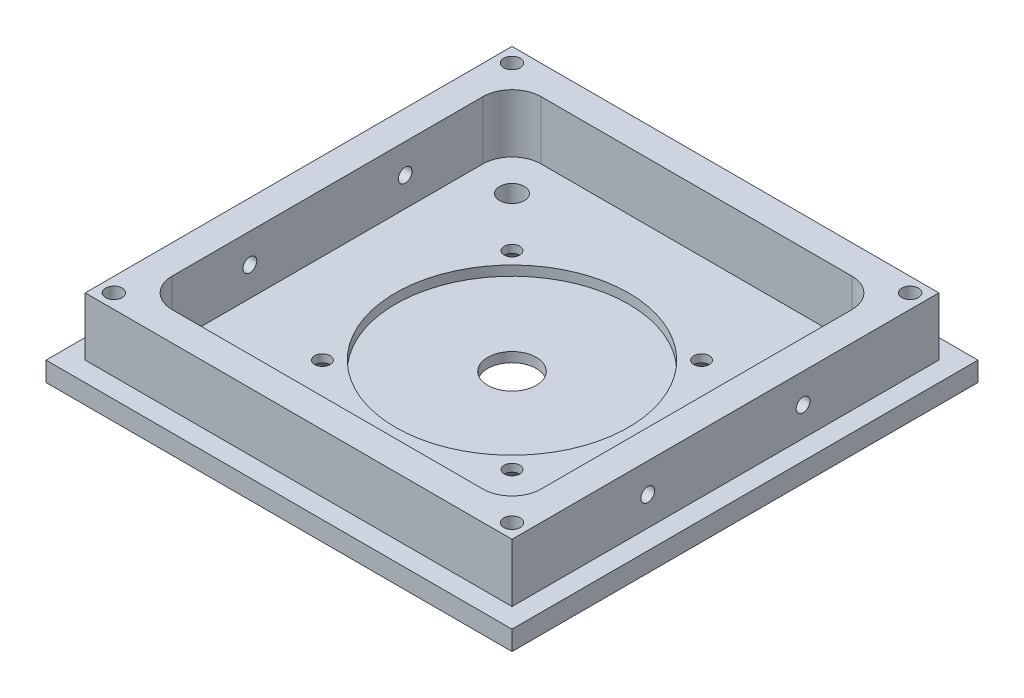
SolidWorks part; units mm, degrees
material "6061-T6 (SS)"
ref_plane "Front Plane" through (0, 0, 0) normal (0, 0, 1) x (1, 0, 0)
ref_plane "Top Plane" through (0, 0, 0) normal (0, 1, 0) x (1, 0, 0)
ref_plane "Right Plane" through (0, 0, 0) normal (1, 0, 0) x (0, 0, -1)
sketch "Sketch1" plane through (0, 0, 0) normal (0, 1, 0) x (1, 0, 0)
  line L1 (-38.1, -38.1) -> (38.1, -38.1)
  line L2 (-38.1, -38.1) -> (-38.1, 38.1)
  line L3 (-38.1, 38.1) -> (38.1, 38.1)
  line L4 (38.1, -38.1) -> (38.1, 38.1)
  line L5 (-38.1, -38.1) -> (38.1, 38.1) construction
  line L6 (-38.1, 38.1) -> (38.1, -38.1) construction
  point P0 (0, 0)
  dimension "D1" = 76.2
  dimension "D2" = 76.2
extrude "Boss-Extrude1" add sketch "Sketch1" along normal blind 3.175
sketch "Sketch2" plane through (0, 3.175, 0) normal (0, 1, 0) x (1, 0, 0)
  line L0 (-38.1, 38.1) -> (-38.1, -38.1) construction
  line L1 (34.8971, -34.8971) -> (-34.8971, -34.8971)
  line L2 (34.8971, -34.8971) -> (34.8971, 34.8971)
  line L3 (34.8971, 34.8971) -> (-34.8971, 34.8971)
  line L4 (-34.8971, -34.8971) -> (-34.8971, 34.8971)
  line L5 (34.8971, -34.8971) -> (-34.8971, 34.8971) construction
  line L6 (34.8971, 34.8971) -> (-34.8971, -34.8971) construction
  line L7 (30.1625, -30.1625) -> (-30.1625, -30.1625)
  line L8 (30.1625, -30.1625) -> (30.1625, 30.1625)
  line L9 (30.1625, 30.1625) -> (-30.1625, 30.1625)
  line L10 (-30.1625, -30.1625) -> (-30.1625, 30.1625)
  line L11 (30.1625, -30.1625) -> (-30.1625, 30.1625) construction
  line L12 (30.1625, 30.1625) -> (-30.1625, -30.1625) construction
  line L14 (38.1, 38.1) -> (-38.1, 38.1) construction
  point P0 (0, 0)
  point P6 (0, 0)
  dimension "D1" = 3.2029
  dimension "D2" = 3.2029
  dimension "D3" = 60.325
extrude "Boss-Extrude2" add sketch "Sketch2" along normal blind 9.525
fillet "Fillet1" radius 4.7625 4 edges at (-30.1625, 7.9375, 30.1625) (30.1625, 7.9375, 30.1625) (30.1625, 7.9375, -30.1625) (-30.1625, 7.9375, -30.1625)
sketch "Sketch3" plane through (0, 3.175, 0) normal (0, 1, 0) x (1, 0, 0)
  circle A0 centre (0, 0) radius 19.05
  dimension "D1" = 38.1
extrude "Cut-Extrude1" cut sketch "Sketch3" against normal blind 1.5875
sketch "Sketch4" plane through (0, 1.5875, 0) normal (0, 1, 0) x (1, 0, 0)
  circle A0 centre (0, 0) radius 3.9688
  dimension "D1" = 7.9375
extrude "Cut-Extrude2" cut sketch "Sketch4" against normal through all
sketch "Sketch5" plane through (0, 3.175, 0) normal (0, 1, 0) x (1, 0, 0)
  line L1 (15.5, -15.5) -> (-15.5, -15.5)
  line L2 (15.5, -15.5) -> (15.5, 15.5)
  line L3 (15.5, 15.5) -> (-15.5, 15.5)
  line L4 (-15.5, -15.5) -> (-15.5, 15.5)
  line L5 (15.5, -15.5) -> (-15.5, 15.5) construction
  line L6 (15.5, 15.5) -> (-15.5, -15.5) construction
  line L7 (23.5966, -23.5966) -> (-23.5966, -23.5966)
  line L8 (23.5966, -23.5966) -> (23.5966, 23.5966)
  line L9 (23.5966, 23.5966) -> (-23.5966, 23.5966)
  line L10 (-23.5966, -23.5966) -> (-23.5966, 23.5966)
  line L11 (23.5966, -23.5966) -> (-23.5966, 23.5966) construction
  line L12 (23.5966, 23.5966) -> (-23.5966, -23.5966) construction
  circle A0 centre (-15.5, 15.5) radius 1.2637
  circle A1 centre (15.5, 15.5) radius 1.2637
  circle A2 centre (15.5, -15.5) radius 1.2637
  circle A3 centre (-15.5, -15.5) radius 1.2637
  point P2 (0, 0)
  point P10 (0, 0)
  dimension "D2" = 2.5273
  dimension "D1" = 31
  dimension "D3" = 47.1932
hole_wizard "#39 (0.0995) Diameter Hole1" positions "Sketch7" profile "Sketch6" hole size "#39" standard "ANSI Inch" end condition through all
sketch "Sketch7" plane through (0, 3.175, 0) normal (0, 1, 0) x (1, 0, 0)
  point P0 (15.5, 15.5)
  point P3 (-15.5, 15.5)
  point P6 (-15.5, -15.5)
  point P9 (15.5, -15.5)
  point P12 (-23.5966, 23.5966)
  point P15 (23.5966, 23.5966)
  point P18 (23.5966, -23.5966)
  point P21 (-23.5966, -23.5966)
sketch "Sketch6" plane through (15.5, 3.175, -15.5) normal (1, 0, 0) x (0, 0, 1)
  line L0 (0, 0) -> (0, 3.175)
  line L1 (0, 3.175) -> (1.2636, 3.175)
  line L2 (1.2636, 3.175) -> (1.2636, 0)
  line L5 (1.2636, 0) -> (0, 0)
  line L11 (0, -6.35) -> (0, 107.95) construction
  dimension "Thru Hole Dia." = 2.5273
  dimension "Thru Hole Depth" = 3.175
hole_wizard "#10-32 Tapped Hole1" positions "Sketch17" profile "Sketch15" tap size "#10-32" standard "ANSI Inch" end condition through all
sketch "Sketch17" plane through (0, 3.175, 0) normal (0, 1, 0) x (1, 0, 0)
  point P0 (-23.5966, 23.5966)
  point P3 (23.5966, 23.5966)
  point P6 (23.5966, -23.5966)
  point P9 (-23.5966, -23.5966)
sketch "Sketch15" plane through (-23.5966, 3.175, -23.5966) normal (1, 0, 0) x (0, 0, 1)
  line L0 (0, 0) -> (0, 3.175)
  line L1 (0, 3.175) -> (2.0193, 3.175)
  line L2 (2.0193, 3.175) -> (2.0193, 0)
  line L5 (2.0193, 0) -> (0, 0)
  line L11 (0, -6.35) -> (0, 107.95) construction
  dimension "Thru Tap Drill Dia." = 4.0386
  dimension "Thru Tap Drill Depth" = 3.175
cosmetic thread "Hole Thread3" parameters "D2"=4.826
cosmetic thread "Hole Thread4" parameters "D2"=4.826
cosmetic thread "Hole Thread5" parameters "D2"=4.826
cosmetic thread "Hole Thread6" parameters "D2"=4.826
sketch "Sketch8" plane through (34.8971, 0, 0) normal (1, 0, 0) x (0, 0, -1)
  line L0 (-38.1, 3.175) -> (38.1, 3.175) construction
  point P0 (-12.7, 7.9375)
  dimension "D1" = 4.7625
  dimension "D2" = 12.7
hole_wizard "#4-40 Tapped Hole1" positions "Sketch10" profile "Sketch9" tap size "#4-40" standard "ANSI Inch"
sketch "Sketch10" plane through (34.8971, 0, 0) normal (1, 0, 0) x (0, 0, -1)
  point P0 (-12.7, 7.9375)
sketch "Sketch9" plane through (34.8971, 7.9375, 12.7) normal (0, 1, 0) x (0, 0, -1)
  line L0 (0, 0) -> (0, 7.2832)
  line L1 (0, 7.2832) -> (1.1303, 6.604)
  line L2 (1.1303, 6.604) -> (1.1303, 0)
  line L5 (1.1303, 0) -> (0, 0)
  line L10 (0, 7.2832) -> (-1.1303, 6.604) construction
  line L11 (0, -6.35) -> (0, 107.95) construction
  dimension "Tap Drill Dia." = 2.2606
  dimension "Tap Drill Depth" = 6.604
  dimension "Drill Angle" = 118
cosmetic thread "Hole Thread1" parameters "D1"=2.4486, "D2"=2.8448
mirror "Mirror1" about plane through (0, 0, 0) normal (0, 0, 1) of "#4-40 Tapped Hole1"
mirror "Mirror2" about plane through (0, 0, 0) normal (1, 0, 0) of "Mirror1"
chamfer "Chamfer1" distance 1.905 angle 41 4 edges at (-15.5, 0, -14.2363) (15.5, 0, -14.2364) (15.5, 0, 16.7636) (-15.5, 0, 16.7637) first distance on face at (-15.5, 0, -14.2363) first distance on face at (15.5, 0, -14.2364) first distance on face at (15.5, 0, 16.7636) first distance on face at (-15.5, 0, 16.7637)
sketch "Sketch11" plane through (0, 0, 0) normal (0, -1, 0) x (1, 0, 0)
  circle A0 centre (32.5501, -32.5501) radius 2.032
  dimension "D1" = 4.064
hole_wizard "#6-32 Tapped Hole1" positions "Sketch13" profile "Sketch12" tap size "#6-32" standard "ANSI Inch" end condition through all
sketch "Sketch13" plane through (0, 0, 0) normal (0, -1, 0) x (-1, 0, 0)
  point P0 (-32.5501, 32.5501)
sketch "Sketch12" plane through (32.5501, 0, -32.5501) normal (1, 0, 0) x (0, 0, -1)
  line L0 (0, 0) -> (0, 12.7)
  line L1 (0, 12.7) -> (1.3525, 12.7)
  line L2 (1.3525, 12.7) -> (1.3525, 0)
  line L5 (1.3525, 0) -> (0, 0)
  line L11 (0, -6.35) -> (0, 107.95) construction
  dimension "Thru Tap Drill Dia." = 2.7051
  dimension "Thru Tap Drill Depth" = 12.7
cosmetic thread "Hole Thread2" parameters "D2"=3.5052
pattern_circular "CirPattern1" count 4 over 360 about axis through (0, 0, 0) along (0, 1, 0) of "#6-32 Tapped Hole1"
equation "\"D2@Sketch2\"=\"D1@Sketch2\""
equation "\"D2@Sketch1\"=\"D1@Sketch1\""
